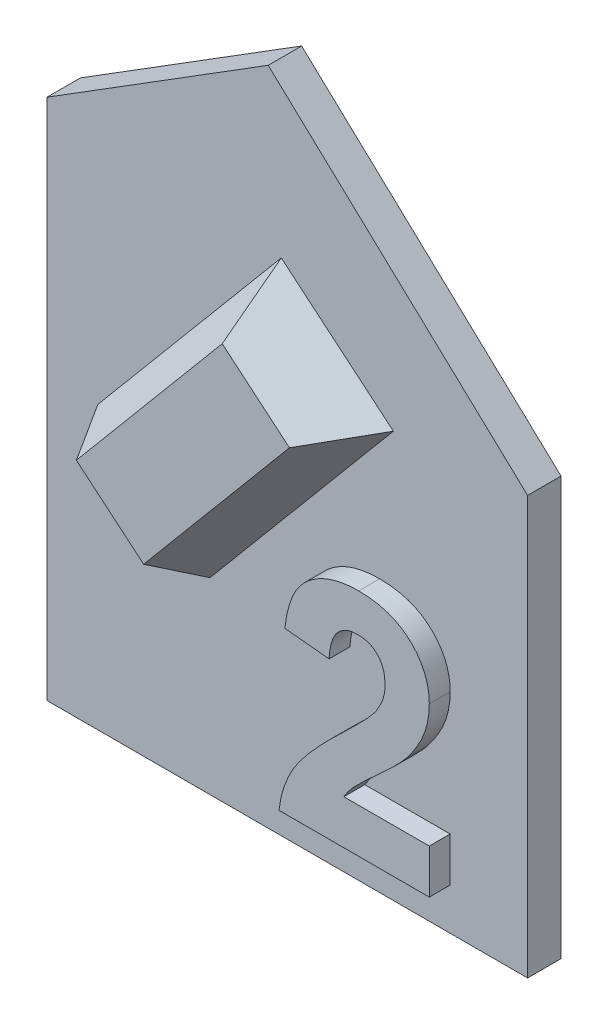
SolidWorks part; units mm, degrees
ref_plane "Přední rovina" through (0, 0, 0) normal (0, 0, 1) x (1, 0, 0)
ref_plane "Horní rovina" through (0, 0, 0) normal (0, 1, 0) x (1, 0, 0)
ref_plane "Pravá rovina" through (0, 0, 0) normal (1, 0, 0) x (0, 0, -1)
sketch "Skica1" plane through (0, 0, 0) normal (0, 0, 1) x (1, 0, 0)
  line L0 (-66.5051, 0) -> (66.5051, 0) construction
  line L1 (0, 0) -> (0, 20)
  line L2 (0, 20) -> (-12.4128, 31.6156)
  line L3 (-12.4128, 31.6156) -> (-23, 25)
  line L4 (-23, 25) -> (-23, 0)
  line L5 (-23, 0) -> (0, 0)
  dimension "D1" = 23
  dimension "D2" = 25
  dimension "D3" = 20
  dimension "D4" = 17
  dimension "D5" = 122
extrude "Přidat vysunutím5" add sketch "Skica1" along normal blind 1.6
sketch "Skica2" plane through (0, 0, 1.6) normal (0, 0, 1) x (1, 0, 0)
  line L1 (-23, 25) -> (-23, 0) construction
  line L2 (0, 0) -> (0, 20) construction
  line L3 (-3, 0) -> (-3, 22.8073) construction
  line L4 (-23, 0) -> (0, 0) construction
  line L5 (0, 20) -> (-12.4128, 31.6156) construction
  line L6 (-23, 2) -> (-3, 2) construction
  text T1 "2" font "Arial" height 11
  dimension "D2" = 3
  dimension "D3" = 2
extrude "Přidat vysunutím6" add sketch "Skica2" along normal blind 1
sketch "Skica3" plane through (0, 0, 1.6) normal (0, 0, 1) x (1, 0, 0)
  line L0 (-23, -0.3065) -> (-3.339, 23.1246) construction
  line L1 (-23, 25) -> (-23, 0) construction
  line L2 (0, 20) -> (-12.4128, 31.6156) construction
  line L3 (0, 0) -> (0, 20) construction
  line L4 (-23, 0) -> (0, 0) construction
  line L5 (-15.2007, 8.9884) -> (-6.4244, 19.4476)
  line L6 (-6.4244, 19.4476) -> (-11.7867, 23.9471)
  line L7 (-11.7867, 23.9471) -> (-20.563, 13.4879)
  line L8 (-20.563, 13.4879) -> (-15.2007, 8.9884)
  dimension "D1" = 3.339
  dimension "D2" = 50
  dimension "D3" = 7
  dimension "D4" = 13.6535
  dimension "D5" = 4.8
extrude "Přidat vysunutím7" add sketch "Skica3" along normal blind 3
chamfer "Zkosení1" distance 3 angle 25 4 edges at (-17.8818, 11.2382, 4.6) (-16.1748, 18.7175, 4.6) (-9.1055, 21.6973, 4.6) (-10.8125, 14.218, 4.6) first distance on face at (-17.8818, 11.2382, 3.1) first distance on face at (-16.1748, 18.7175, 3.1) first distance on face at (-9.1055, 21.6973, 3.1) first distance on face at (-10.8125, 14.218, 3.1)
